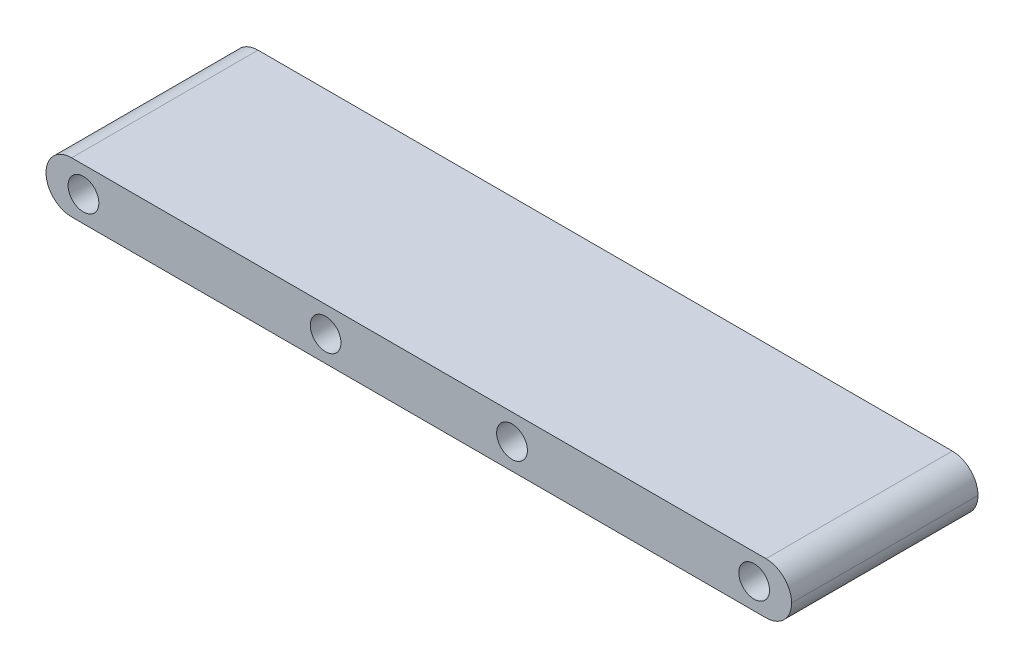
SolidWorks part; units mm, degrees
ref_plane "前视基准面" through (0, 0, 0) normal (0, 0, 1) x (1, 0, 0)
ref_plane "上视基准面" through (0, 0, 0) normal (0, 1, 0) x (1, 0, 0)
ref_plane "右视基准面" through (0, 0, 0) normal (1, 0, 0) x (0, 0, -1)
sketch "草图1" plane through (0, 0, 0) normal (0, 0, 1) x (1, 0, 0)
  line L0 (0, 0) -> (800, 0)
  line L1 (0, 0) -> (0, 55)
  line L2 (0, 55) -> (800, 55)
  line L3 (800, 55) -> (800, 0)
  circle A0 centre (300, 27.5) radius 16.5
  circle A1 centre (500, 27.5) radius 16.5
  dimension "D6" = 33
  dimension "D7" = 33
  dimension "D1" = 800
  dimension "D2" = 55
  dimension "D3" = 300
  dimension "D4" = 300
  dimension "D5" = 27.5
extrude "凸台-拉伸1" add sketch "草图1" along normal blind 200
sketch "草图2" plane through (0, 0, 200) normal (0, 0, 1) x (1, 0, 0)
  line L2 (800, 55) -> (0, 55) construction
  line L4 (0, 55) -> (0, 0) construction
  line L5 (800, 0) -> (800, 55) construction
  circle A0 centre (759.8076, 27.5) radius 16.5
  circle A1 centre (40.1924, 27.5) radius 16.5
  dimension "D1" = 33
  dimension "D2" = 33
  dimension "D3" = 27.5
  dimension "D4" = 40.1924
  dimension "D5" = 27.5
  dimension "D6" = 40.1924
extrude "切除-拉伸1" cut sketch "草图2" against normal through all
fillet "圆角1" radius 27.5 4 edges at (0, 0, 100) (0, 55, 100) (800, 0, 100) (800, 55, 100)
